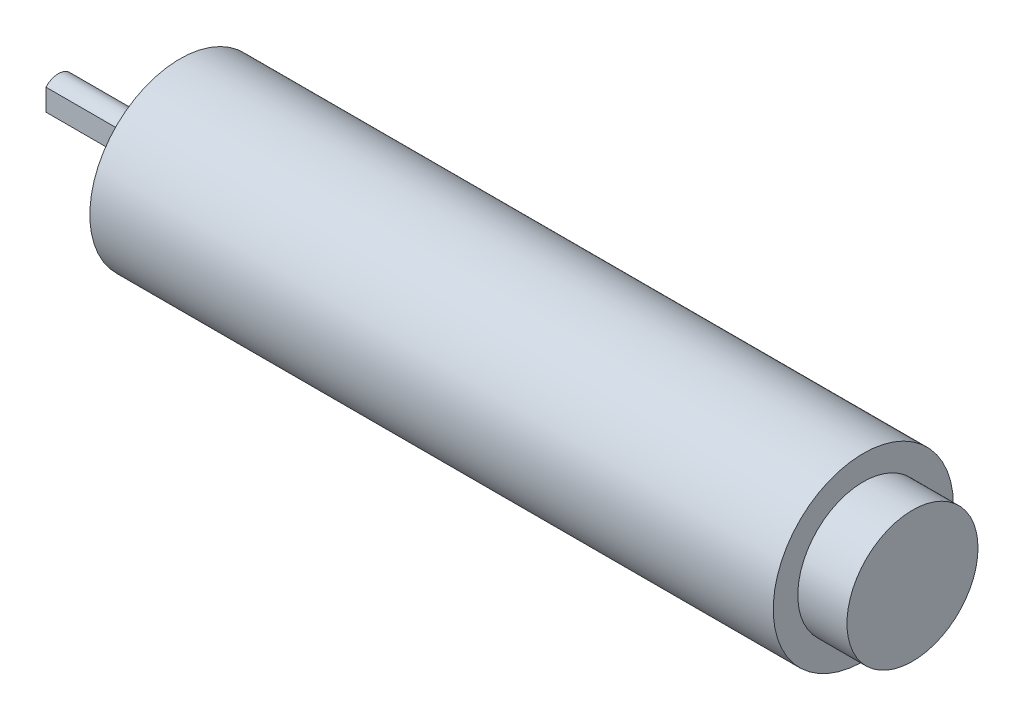
SolidWorks part; units mm, degrees
ref_plane "Front Plane" through (0, 0, 0) normal (0, 0, 1) x (1, 0, 0)
ref_plane "Top Plane" through (0, 0, 0) normal (0, 1, 0) x (1, 0, 0)
ref_plane "Right Plane" through (0, 0, 0) normal (1, 0, 0) x (0, 0, -1)
sketch "Sketch1" plane through (0, 0, 0) normal (0, 0, 1) x (1, 0, 0)
  line L0 (0, 11) -> (0, 0)
  line L1 (0, 0) -> (52.6, 0)
  line L2 (52.6, 0) -> (52.6, 11)
  line L3 (52.6, 11) -> (0, 11)
  line L4 (0, 0) -> (52.6, 0) construction
revolve "Revolve1" add sketch "Sketch1" angle 360 about L4 reverse direction yes
sketch "Sketch2" plane through (0, 0, 0) normal (-1, 0, 0) x (0, 0, 1)
  circle A0 centre (0, 0) radius 5
extrude "Boss-Extrude1" add sketch "Sketch2" along normal blind 1.35
sketch "Sketch3" plane through (-1.35, 0, 0) normal (-1, 0, 0) x (0, 0, 1)
  circle A0 centre (0, 0) radius 3.5
extrude "Boss-Extrude2" add sketch "Sketch3" along normal blind 1.8
sketch "Sketch4" plane through (-3.15, 0, 0) normal (-1, 0, 0) x (0, 0, 1)
  circle A0 centre (0, 0) radius 2
extrude "Boss-Extrude3" add sketch "Sketch4" along normal blind 11.7
ref_plane "Plane1" through (-3.675, 0, 3.675) normal (0.7071, 0, -0.7071) x (0, 1, 0)
sketch "Sketch6" plane through (-14.85, 0, 0) normal (-1, 0, 0) x (0, 0, 1)
  line L0 (1.5, 1.3229) -> (1.5, -1.3229)
  arc A0 (1.5, -1.3229) -> (1.5, 1.3229) centre (0, 0) ccw
extrude "Cut-Extrude1" cut sketch "Sketch6" against normal up to surface up to plane "Plane1"
hole_wizard "Hole1" positions "Sketch8" profile "Sketch7" legacy
sketch "Sketch8" plane through (0, 0, 0) normal (-1, 0, 0) x (0, 0, 1)
  point P0 (7, 0)
sketch "Sketch7" plane through (0, 0, 7) normal (0, 1, 0) x (0, 0, 1)
  line L0 (0, 0) -> (0, 6.5)
  line L1 (0, 6.5) -> (0.975, 6.5)
  line L2 (0.975, 6.5) -> (0.975, 0)
  line L3 (0.975, 0) -> (0, 0)
  line L4 (0, 110) -> (0, -10) construction
  dimension "Diameter" = 1.95
  dimension "Depth" = 6.5
hole_wizard "Hole2" positions "Sketch10" profile "Sketch9" legacy
sketch "Sketch10" plane through (0, 0, 0) normal (-1, 0, 0) x (0, 0, 1)
  point P0 (-3.5, -6.0622)
sketch "Sketch9" plane through (0, -6.0622, -3.5) normal (0, 1, 0) x (0, 0, 1)
  line L0 (0, 0) -> (0, 6.5)
  line L1 (0, 6.5) -> (0.975, 6.5)
  line L2 (0.975, 6.5) -> (0.975, 0)
  line L3 (0.975, 0) -> (0, 0)
  line L4 (0, 110) -> (0, -10) construction
  dimension "Diameter" = 1.95
  dimension "Depth" = 6.5
hole_wizard "Hole3" positions "Sketch12" profile "Sketch11" legacy
sketch "Sketch12" plane through (0, 0, 0) normal (-1, 0, 0) x (0, 0, 1)
  point P0 (-3.5, 6.0622)
sketch "Sketch11" plane through (0, 6.0622, -3.5) normal (0, 1, 0) x (0, 0, 1)
  line L0 (0, 0) -> (0, 6.5)
  line L1 (0, 6.5) -> (0.975, 6.5)
  line L2 (0.975, 6.5) -> (0.975, 0)
  line L3 (0.975, 0) -> (0, 0)
  line L4 (0, 110) -> (0, -10) construction
  dimension "Diameter" = 1.95
  dimension "Depth" = 6.5
hole_wizard "Hole4" positions "Sketch14" profile "Sketch13" legacy
sketch "Sketch14" plane through (52.6, 0, 0) normal (1, 0, 0) x (0, 0, -1)
  point P0 (0, 0)
sketch "Sketch13" plane through (52.6, 0, 0) normal (0, 1, 0) x (0, 0, -1)
  line L0 (0, 0) -> (0, 6.4)
  line L1 (0, 6.4) -> (3.5, 6.4)
  line L2 (3.5, 6.4) -> (3.5, 0)
  line L3 (3.5, 0) -> (0, 0)
  line L4 (0, 110) -> (0, -10) construction
  dimension "Diameter" = 7
  dimension "Depth" = 6.4
hole_wizard "Hole5" positions "Sketch16" profile "Sketch15" legacy
sketch "Sketch16" plane through (52.6, 0, 0) normal (1, 0, 0) x (0, 0, -1)
  point P0 (-8.5, 0)
sketch "Sketch15" plane through (52.6, 0, 8.5) normal (0, 1, 0) x (0, 0, -1)
  line L0 (0, 0) -> (0, 3)
  line L1 (0, 3) -> (1.05, 3)
  line L2 (1.05, 3) -> (1.05, 0)
  line L3 (1.05, 0) -> (0, 0)
  line L4 (0, 110) -> (0, -10) construction
  dimension "Diameter" = 2.1
  dimension "Depth" = 3
hole_wizard "Hole6" positions "Sketch18" profile "Sketch17" legacy
sketch "Sketch18" plane through (52.6, 0, 0) normal (1, 0, 0) x (0, 0, -1)
  point P0 (4.25, -7.3612)
sketch "Sketch17" plane through (52.6, -7.3612, -4.25) normal (0, 1, 0) x (0, 0, -1)
  line L0 (0, 0) -> (0, 3)
  line L1 (0, 3) -> (1.05, 3)
  line L2 (1.05, 3) -> (1.05, 0)
  line L3 (1.05, 0) -> (0, 0)
  line L4 (0, 110) -> (0, -10) construction
  dimension "Diameter" = 2.1
  dimension "Depth" = 3
hole_wizard "Hole7" positions "Sketch20" profile "Sketch19" legacy
sketch "Sketch20" plane through (52.6, 0, 0) normal (1, 0, 0) x (0, 0, -1)
  point P0 (4.25, 7.3612)
sketch "Sketch19" plane through (52.6, 7.3612, -4.25) normal (0, 1, 0) x (0, 0, -1)
  line L0 (0, 0) -> (0, 3)
  line L1 (0, 3) -> (1.05, 3)
  line L2 (1.05, 3) -> (1.05, 0)
  line L3 (1.05, 0) -> (0, 0)
  line L4 (0, 110) -> (0, -10) construction
  dimension "Diameter" = 2.1
  dimension "Depth" = 3
ref_plane "Plane2" through (52.6, 0, 0) normal (1, 0, 0) x (0, 0, -1)
sketch "Sketch25" plane through (52.6, 0, 0) normal (1, 0, 0) x (0, 0, -1)
  circle A0 centre (0, 0) radius 11
extrude "Boss-Extrude4" add sketch "Sketch25" along normal blind 36.83
sketch "Sketch26" plane through (89.43, 0, 0) normal (1, 0, 0) x (0, 0, -1)
  circle A0 centre (0, 0) radius 8
  circle A1 centre (0, 0) radius 12
  dimension "D1" = 16
  dimension "D2" = 24
extrude "Cut-Extrude2" cut sketch "Sketch26" against normal blind 6
